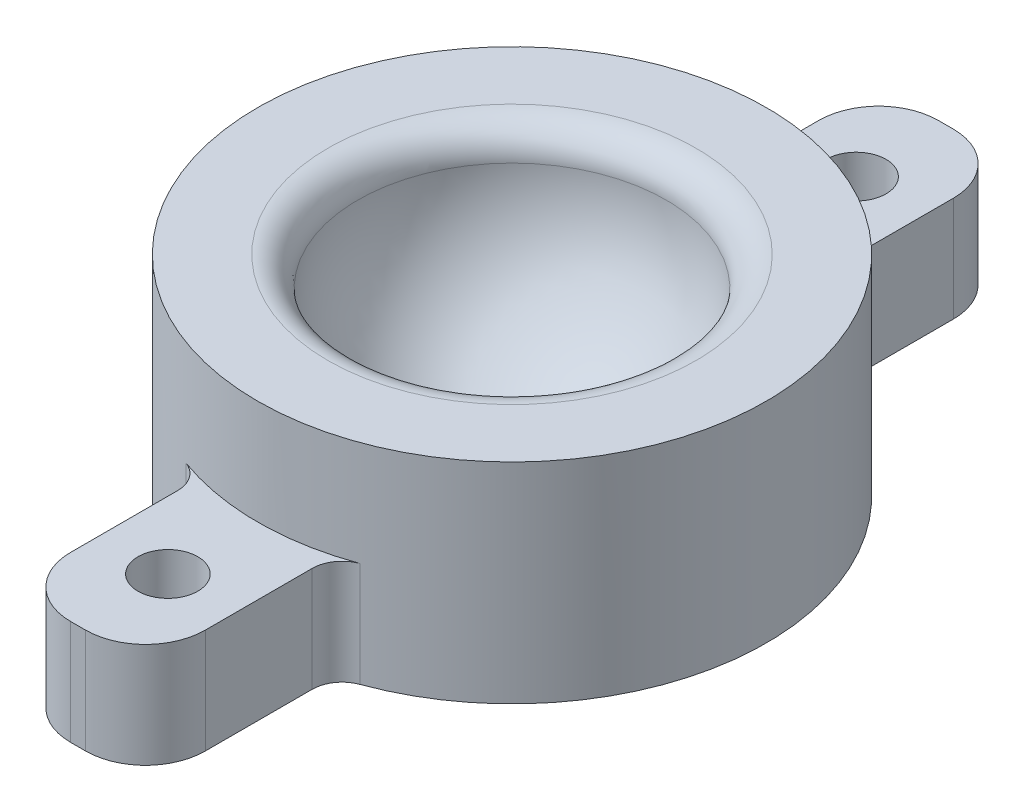
SolidWorks part; units mm, degrees
ref_plane "Alzado" through (0, 0, 0) normal (0, 0, 1) x (1, 0, 0)
ref_plane "Planta" through (0, 0, 0) normal (0, 1, 0) x (1, 0, 0)
ref_plane "Vista lateral" through (0, 0, 0) normal (1, 0, 0) x (0, 0, -1)
sketch "Croquis1" plane through (0, 0, 0) normal (0, 1, 0) x (1, 0, 0)
  line L0 (-2.25, 8.1968) -> (-2.25, 12.5)
  line L1 (-0.25, 14.5) -> (0.25, 14.5)
  line L2 (2.25, 12.5) -> (2.25, 8.1968)
  line L3 (-55, 0) -> (55, 0) construction
  line L4 (2.25, -12.5) -> (2.25, -8.1968)
  line L5 (-2.25, -8.1968) -> (-2.25, -12.5)
  line L6 (-0.25, -14.5) -> (0.25, -14.5)
  circle A0 centre (0, 0) radius 8.5
  circle A1 centre (0, 11.5) radius 1
  arc A2 (0.25, 14.5) -> (2.25, 12.5) centre (0.25, 12.5) cw
  arc A3 (-2.25, 12.5) -> (-0.25, 14.5) centre (-0.25, 12.5) cw
  arc A4 (-2.25, -12.5) -> (-0.25, -14.5) centre (-0.25, -12.5) ccw
  arc A5 (0.25, -14.5) -> (2.25, -12.5) centre (0.25, -12.5) ccw
  circle A6 centre (0, -11.5) radius 1
  point P10 (2.25, 14.5)
  point P12 (0, 14.5)
  point P14 (-2.25, 14.5)
  point P28 (-2.25, -14.5)
  point P29 (2.25, -14.5)
  dimension "D1" = 2
  dimension "D2" = 17
  dimension "D6" = 2
  dimension "D3" = 14.5
  dimension "D4" = 4.5
  dimension "D5" = 11.5
extrude "Saliente-Extruir1" add sketch "Croquis1" along normal blind 3.5 contours A3 L0 A0 L2 A2 L1 A1 | A0 | L6 A5 L4 A0 L5 A4 A6 region at (-2.1726, 0, -10.3484) region at (0, 0, 0) region at (0, 0, 8.5774)
extrude "Saliente-Extruir2" add sketch "Croquis1<3>" along normal blind 7 contours A0 region at (0, 0, 0)
sketch "Croquis1<3>" plane through (0, 0, 0) normal (0, 1, 0) x (1, 0, 0) same geometry as "Croquis1"
fillet "Redondeo1" radius 1 4 edges at (2.25, 1.75, -8.1968) (2.25, 1.75, 8.1968) (-2.25, 1.75, 8.1968) (-2.25, 1.75, -8.1968)
sketch "Croquis2" plane through (0, 0, 0) normal (0, 0, 1) x (1, 0, 0)
  line L0 (0, 11.15) -> (0, 0.85)
  arc A0 (0, 11.15) -> (0, 0.85) centre (0, 6) ccw
  dimension "D1" = 10.3
  dimension "D2" = 6
revolve "Cortar-Revolución1" cut sketch "Croquis2" angle 360 about L0
fillet "Redondeo3" radius 1 1 edges at (0, 7, 5.052)
